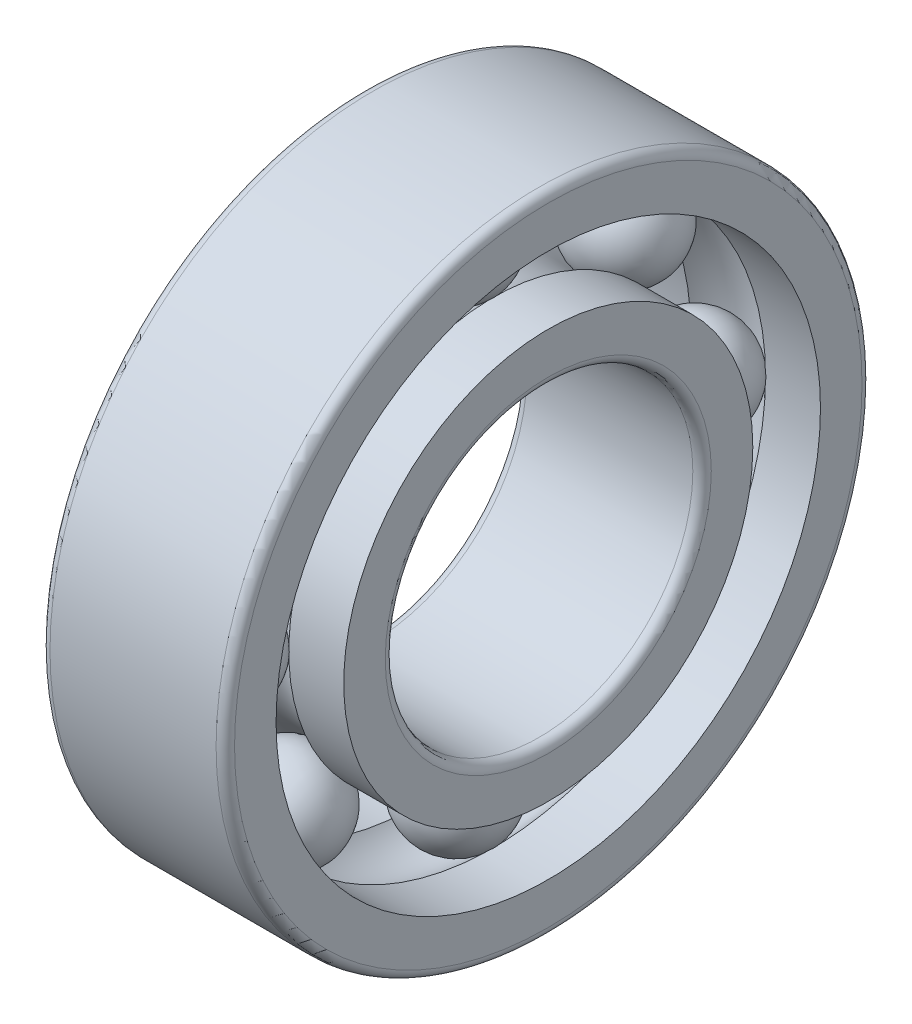
SolidWorks part; units mm, degrees
ref_plane "Plane1" through (0, 0, 0) normal (0, 0, 1) x (1, 0, 0)
ref_plane "Plane2" through (0, 0, 0) normal (0, 1, 0) x (1, 0, 0)
ref_plane "Plane3" through (0, 0, 0) normal (1, 0, 0) x (0, 0, -1)
ref_axis "Axis1" through (-50, 0, 0) along (1, 0, 0)
sketch "BalDetSke" plane through (0, 0, 0) normal (0, 0, 1) x (1, 0, 0)
  line L0 (-3.3, 15.5) -> (3.3, 15.5)
  line L1 (-1.905, 15.5) -> (1.905, 15.5) construction
  line L2 (0, 0) -> (0, 25) construction
  arc A0 (3.3, 15.5) -> (-3.3, 15.5) centre (0, 15.5) cw
  dimension "Ball_diameter" = 6.6
  dimension "BallCLRad" = 15.5
revolve "BallDetailed" add sketch "BalDetSke" angle 360 about L1 reverse direction yes
sketch "InnRacSke" plane through (0, 0, 0) normal (0, 0, 1) x (1, 0, 0)
  line L0 (-2.426, 13.3) -> (-6, 13.3)
  line L1 (-6, 13.3) -> (-6, 10.6)
  line L2 (-5.4, 10) -> (5.4, 10)
  line L3 (6, 10.6) -> (6, 13.3)
  line L4 (6, 13.3) -> (2.426, 13.3)
  line L5 (-20.6375, 0) -> (20.6375, 0) construction
  line L6 (0, 0) -> (0, 30) construction
  arc A0 (-6, 10.6) -> (-5.4, 10) centre (-5.4, 10.6) ccw
  arc A1 (5.4, 10) -> (6, 10.6) centre (5.4, 10.6) ccw
  arc A2 (2.426, 13.3) -> (-2.426, 13.3) centre (0, 15.5) cw
  dimension "Fillet_radius" = 0.6
  dimension "Ball_diameter" = 6.55
  dimension "ID" = 20
  dimension "OD" = 26.6
  dimension "Width" = 12
  dimension "BallCLRad" = 15.5
revolve "InnerRace" add sketch "InnRacSke" angle 360 about L5 reverse direction yes
sketch "OutRacSke" plane through (0, 0, 0) normal (0, 0, 1) x (1, 0, 0)
  line L0 (-2.426, 17.7) -> (-6, 17.7)
  line L1 (-6, 17.7) -> (-6, 20.4)
  line L2 (-5.4, 21) -> (5.4, 21)
  line L3 (6, 20.4) -> (6, 17.7)
  line L4 (6, 17.7) -> (2.426, 17.7)
  line L5 (-20.6375, 0) -> (20.6375, 0) construction
  line L6 (0, 0) -> (0, 30) construction
  arc A0 (-6, 20.4) -> (-5.4, 21) centre (-5.4, 20.4) cw
  arc A1 (5.4, 21) -> (6, 20.4) centre (5.4, 20.4) cw
  arc A2 (2.426, 17.7) -> (-2.426, 17.7) centre (0, 15.5) ccw
  dimension "Fillet_radius" = 0.6
  dimension "Ball_diameter" = 6.55
  dimension "OD" = 42
  dimension "ID" = 35.4
  dimension "Width" = 12
  dimension "BallCLRad" = 15.5
revolve "OuterRace" add sketch "OutRacSke" angle 360 about L5 reverse direction yes
pattern_circular "Répétition circulaire1" count 8 over 360 about axis through (-20.6375, 0, 0) along (1, 0, 0) of bodies 102
sketch "Esquisse1" plane through (0, 0, 0) normal (0, 0, 1) x (1, 0, 0)
  line L1 (-5.888, 17.7798) -> (-5.688, 17.7798)
  line L2 (-5.888, 17.7798) -> (-5.888, 13.2851)
  line L3 (-5.888, 13.2851) -> (-5.688, 13.2851)
  line L4 (-5.688, 17.7798) -> (-5.688, 13.2851)
  dimension "D1" = 0.2
revolve "Révolution1" add sketch "Esquisse1" angle 360 about axis through (-20.6375, 0, 0) along (1, 0, 0)
